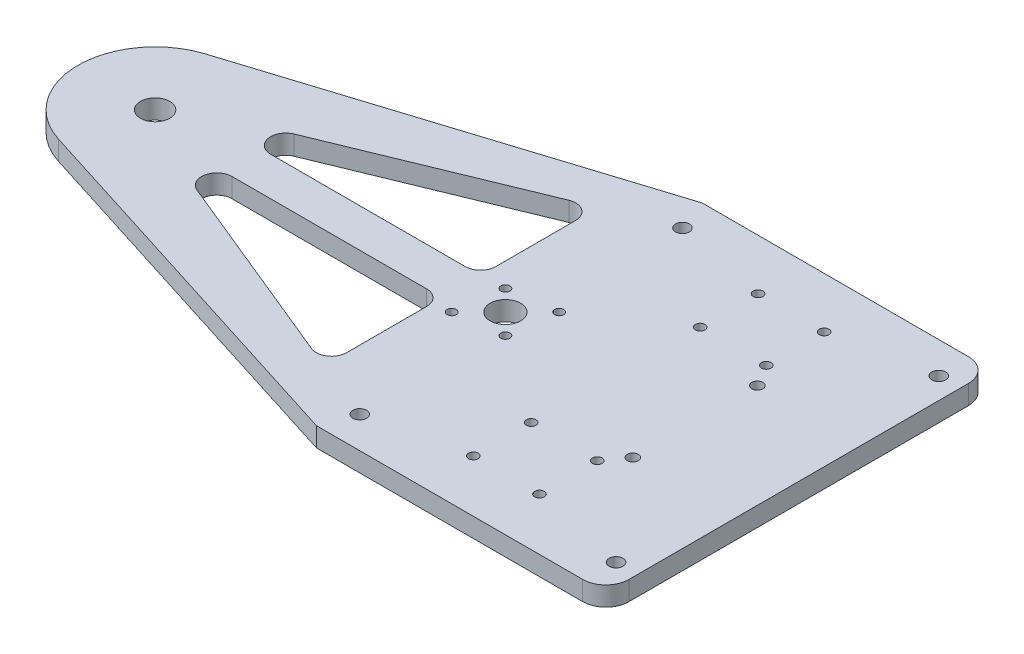
SolidWorks part; units mm, degrees
ref_plane "Front Plane" through (0, 0, 0) normal (0, 0, 1) x (1, 0, 0)
ref_plane "Top Plane" through (0, 0, 0) normal (0, 1, 0) x (1, 0, 0)
ref_plane "Right Plane" through (0, 0, 0) normal (1, 0, 0) x (0, 0, -1)
sketch "Sketch1" plane through (0, 0, 0) normal (0, 1, 0) x (1, 0, 0)
  line L0 (-47.625, 0) -> (47.625, 0) construction
  line L1 (-47.625, -63.5) -> (47.625, -63.5)
  line L2 (-47.625, -63.5) -> (-47.625, 63.5)
  line L3 (-47.625, 63.5) -> (47.625, 63.5)
  line L4 (47.625, -63.5) -> (47.625, 63.5)
  line L5 (-47.625, -63.5) -> (47.625, 63.5) construction
  line L6 (-47.625, 63.5) -> (47.625, -63.5) construction
  point P0 (0, 0)
  dimension "D1" = 95.25
  dimension "D2" = 127
  dimension "D3" = 63.5
extrude "Boss-Extrude1" add sketch "Sketch1" along normal blind 6.35
sketch "Sketch4" plane through (0, 6.35, 0) normal (0, 1, 0) x (1, 0, 0)
  line L1 (-47.625, 63.5) -> (-171.916, 24.2193)
  line L5 (-47.625, 63.5) -> (-47.625, -63.5) construction
  line L9 (-47.625, -63.5) -> (-171.916, -24.2193)
  line L10 (-47.625, 63.5) -> (-47.625, -63.5)
  arc A0 (-171.916, 24.2193) -> (-171.916, -24.2193) centre (-164.2618, 0) ccw
  circle A1 centre (-48.9458, 0) radius 2.5 construction
  dimension "D1" = 50.8
  dimension "D2" = 115.316
extrude "Boss-Extrude3" add sketch "Sketch4" against normal blind 6.35
sketch "Sketch5" plane through (0, 6.35, 0) normal (0, 1, 0) x (1, 0, 0)
  line L0 (-48.9458, 0) -> (-31.7264, 0) construction
  line L3 (-48.9458, 0) -> (-91.3931, 0) construction
  circle A0 centre (-164.2618, 0) radius 4.826
  circle A1 centre (-48.9458, 0) radius 5.04
  arc A2 (-171.916, 24.2193) -> (-171.916, -24.2193) centre (-164.2618, 0) ccw construction
  arc A3 (-171.916, 24.2193) -> (-171.916, -24.2193) centre (-164.2618, 0) ccw
  circle A4 centre (-42.2283, -6.7175) radius 1.5
  circle A5 centre (-40.107, 8.8388) radius 1.5
  circle A6 centre (-57.7846, -8.8388) radius 1.5
  circle A7 centre (-55.6633, 6.7175) radius 1.5
  circle A8 centre (-40.107, 8.8388) radius 1.5 construction
  circle A9 centre (-55.6633, 6.7175) radius 1.5 construction
  circle A10 centre (-57.7846, -8.8388) radius 1.5 construction
  circle A11 centre (-42.2283, -6.7175) radius 1.5 construction
  point P20 (-48.9458, 0)
  dimension "D1" = 9.652
  dimension "D2" = 17.2194
  dimension "D4" = 48.9458
  dimension "D3" = 10.08
extrude "Cut-Extrude1" cut sketch "Sketch5" against normal through all contours A0 | A1 | A5 | A6 | A7 | A4 region at (-164.2618, 6.35, 0) region at (-48.9458, 6.35, 0)
sketch "Sketch6" plane through (0, 6.35, 0) normal (0, 1, 0) x (1, 0, 0)
  line L0 (-63.5, 6.35) -> (-63.5, -6.35) construction
  line L1 (-63.5, 45.1637) -> (-157.9118, 6.35)
  line L2 (-157.9118, 6.35) -> (-63.5, 6.35)
  line L3 (-63.5, 6.35) -> (-63.5, 45.1637)
  line L4 (-63.5, -6.35) -> (-63.5, -45.1637)
  line L5 (-63.5, -45.1637) -> (-157.9118, -6.35)
  line L6 (-157.9118, -6.35) -> (-63.5, -6.35)
  line L7 (0, 0) -> (-63.5, 0) construction
  line L8 (-189.6618, 75.5498) -> (-189.6618, -75.5498) construction
  line L9 (-47.625, 63.5) -> (-171.916, 24.2193) construction
  arc A0 (-171.916, 24.2193) -> (-171.916, -24.2193) centre (-164.2618, 0) ccw construction
  point P12 (-189.6618, 0)
  dimension "D1" = 31.75
  dimension "D2" = 12.7
  dimension "D3" = 12.7
  dimension "D4" = 63.5
extrude "Cut-Extrude2" cut sketch "Sketch6" against normal through all
fillet "Fillet9" radius 5 6 edges at (-157.9118, 3.175, 6.35) (-63.5, 3.175, 6.35) (-63.5, 3.175, 45.1637) (-63.5, 3.175, -6.35) (-157.9118, 3.175, -6.35) (-63.5, 3.175, -45.1637)
fillet "Fillet10" radius 7.62 2 edges at (47.625, 3.175, -63.5) (47.625, 3.175, 63.5)
sketch "Sketch7" plane through (0, 6.35, 0) normal (0, 1, 0) x (1, 0, 0)
  circle A0 centre (-43.7773, -53.1254) radius 2.2812
  circle A1 centre (-43.7773, 53.1254) radius 2.2812
  circle A2 centre (40.6023, 53.1254) radius 2.2812
  circle A3 centre (40.6023, -53.1254) radius 2.2812
  circle A4 centre (-43.7773, 53.1254) radius 2.2812 construction
  circle A5 centre (40.6023, 53.1254) radius 2.2812 construction
  circle A6 centre (40.6023, -53.1254) radius 2.2812 construction
  circle A7 centre (-43.7773, -53.1254) radius 2.2812 construction
extrude "Cut-Extrude3" cut sketch "Sketch7" against normal through all
sketch "Sketch8" plane through (0, 6.35, 0) normal (0, 1, 0) x (1, 0, 0)
  circle A0 centre (-13.2098, -27.25) radius 1.5875
  circle A1 centre (8.5646, -27.25) radius 1.5875
  circle A2 centre (8.5646, -46.3) radius 1.5875
  circle A3 centre (-13.2098, -46.3) radius 1.5875
  circle A4 centre (9.1996, 46.8) radius 1.5875
  circle A5 centre (-12.5748, 27.75) radius 1.5875
  circle A6 centre (-12.5748, 46.8) radius 1.5875
  circle A7 centre (9.1996, 27.75) radius 1.5875
  dimension "D1" = 3.175
extrude "Cut-Extrude4" cut sketch "Sketch8" against normal through all
sketch "Sketch9" plane through (0, 6.35, 0) normal (0, 1, 0) x (1, 0, 0)
  circle A0 centre (13.4994, -20.4978) radius 1.83
  circle A1 centre (13.4995, 20.5026) radius 1.83
extrude "Cut-Extrude5" cut sketch "Sketch9" against normal through all
